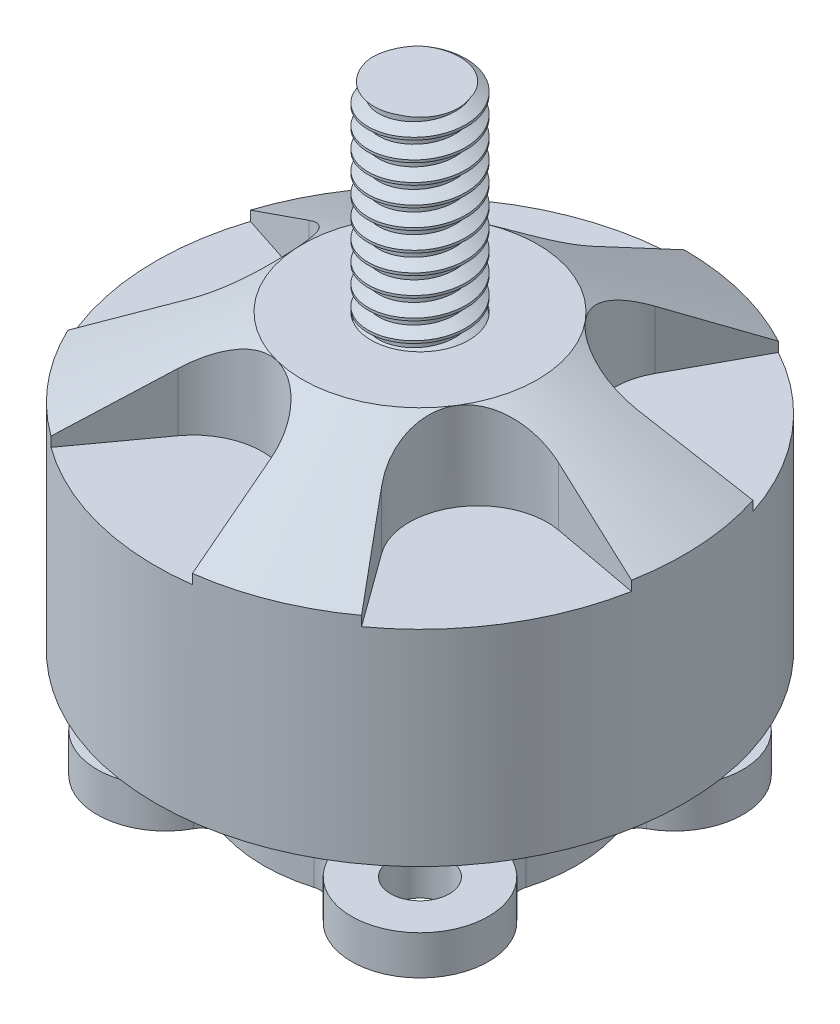
SolidWorks part; units mm, degrees
ref_plane "Front Plane" through (0, 0, 0) normal (0, 0, 1) x (1, 0, 0)
ref_plane "Top Plane" through (0, 0, 0) normal (0, 1, 0) x (1, 0, 0)
ref_plane "Right Plane" through (0, 0, 0) normal (1, 0, 0) x (0, 0, -1)
sketch "Sketch3" plane through (0, 0, 0) normal (0, 1, 0) x (1, 0, 0)
  line L1 (-6.5, 6.5) -> (6.5, -6.5) construction
  line L2 (8, 3.3377) -> (8, -3.3377) construction
  line L3 (-8, 3.3377) -> (-8, -3.3377) construction
  line L4 (-3.3377, -8) -> (3.3377, -8) construction
  line L5 (-3.3377, 8) -> (3.3377, 8) construction
  line L6 (-10, 6.5) -> (-10, -6.5) construction
  line L7 (-6.5, -10) -> (6.5, -10) construction
  line L8 (10, -6.5) -> (10, 6.5) construction
  circle A0 centre (6.5, 6.5) radius 1.5
  circle A1 centre (6.5, -6.5) radius 1.5
  circle A2 centre (-6.5, -6.5) radius 1.5
  circle A3 centre (-6.5, 6.5) radius 1.5
  arc A4 (7.3707, 3.11) -> (3.11, 7.3707) centre (6.5, 6.5) ccw
  arc A5 (3.11, -7.3707) -> (7.3707, -3.11) centre (6.5, -6.5) ccw
  arc A6 (-7.3707, -3.11) -> (-3.11, -7.3707) centre (-6.5, -6.5) ccw
  arc A7 (-3.11, 7.3707) -> (-7.3707, 3.11) centre (-6.5, 6.5) ccw
  arc A8 (-7.3707, 3.11) -> (-7.3707, -3.11) centre (0, 0) ccw
  arc A9 (3.11, 7.3707) -> (-3.11, 7.3707) centre (0, 0) ccw
  arc A10 (7.3707, -3.11) -> (7.3707, 3.11) centre (0, 0) ccw
  arc A12 (-3.11, -7.3707) -> (3.11, -7.3707) centre (0, 0) ccw
  point P15 (0, 0)
  dimension "D3" = 3
  dimension "D4" = 2
  dimension "D5" = 2
  dimension "D1" = 13
  dimension "D2" = 13
  dimension "D6" = 2
  dimension "D7" = 2
  dimension "D8" = 1.5
extrude "Boss-Extrude3" add sketch "Sketch3" along normal blind 2
fillet "Fillet1" radius 1 8 edges at (-7.3707, 1, 3.11) (-7.3707, 1, -3.11) (3.11, 1, -7.3707) (-3.11, 1, -7.3707) (7.3707, 1, 3.11) (7.3707, 1, -3.11) (-3.11, 1, 7.3707) (3.11, 1, 7.3707)
sketch "Sketch4" plane through (0, 2, 0) normal (0, 1, 0) x (1, 0, 0)
  circle A0 centre (0, 0) radius 5
  dimension "D1" = 10
extrude "Boss-Extrude4" add sketch "Sketch4" along normal blind 3.5
sketch "Sketch1" plane through (0, 5.5, 0) normal (0, 1, 0) x (1, 0, 0)
  circle A0 centre (0, 0) radius 13.5
  dimension "D1" = 27
extrude "Boss-Extrude5" add sketch "Sketch1" along normal blind 15
sketch "Sketch5" plane through (0, 20.5, 0) normal (0, 1, 0) x (1, 0, 0)
  circle A0 centre (0, 0) radius 2.5
  dimension "D1" = 5
extrude "Boss-Extrude6" add sketch "Sketch5" along normal blind 10
fillet "Fillet3" radius 1.5 1 edges at (0, 2, 5)
thread "Thread1" pitch 1 method cut profile "Thread Profile1" start angle 0, offset 2, length 15, pitch 1, diameter 5
ref_plane "Plane1" through (-2.5, 32.5, 0) normal (0, 0, 1) x (-1, 0, 0)
sketch "Thread Profile1" plane through (-2.5, 32.5, 0) normal (0, 0, 1) x (-1, 0, 0)
  line L0 (0, 0) -> (0, 1) construction
  line L11 (0, 0) -> (0, 0.875)
  line L12 (0, 0.875) -> (-0.5413, 0.5625)
  line L13 (-0.5413, 0.5625) -> (-0.5413, 0.3125)
  line L15 (-0.5413, 0.3125) -> (0, 0)
  line L17 (-0.5413, 0.4375) -> (0, 0.4375) construction
  point P2 (0, 0)
  dimension "Pitch" = 1
  dimension "Profile_Angle" = 60
  dimension "Profile_Land" = 0.25
  dimension "Profile_Height" = 0.5413
sketch "Sketch6" plane through (0, 0, 0) normal (1, 0, 0) x (0, 0, -1)
  line L0 (-13.5, 16.5) -> (-6, 20.5)
  line L1 (-13.5, 20.5) -> (-13.5, 5.5) construction
  line L2 (13.5, 20.5) -> (-13.5, 20.5) construction
  line L3 (-6, 20.5) -> (-13.5, 20.5)
  line L4 (-13.5, 20.5) -> (-13.5, 16.5)
  line L5 (-13.5, 5.5) -> (13.5, 5.5) construction
  dimension "D1" = 11
  dimension "D2" = 6
ref_axis "Axis1" through (0, 20.5, 0) along (0, -1, 0)
revolve "Cut-Revolve1" cut sketch "Sketch6" angle 360 about axis through (0, 20.5, 0) along (0, -1, 0)
ref_plane "Plane2" through (0, 20.5, 0) normal (0, 1, 0) x (1, 0, 0)
sketch "Sketch7" plane through (0, 20.5, 0) normal (0, 1, 0) x (1, 0, 0)
  line L0 (0, 0) -> (-9.2888, 9.7963)
  line L1 (0, 0) -> (0, 13.5)
  line L2 (0, 0) -> (-5, 12.5399) construction
  circle A0 centre (0, 0) radius 13.5 construction
  circle A1 centre (0, 0) radius 6 construction
  arc A2 (0, 6) -> (-4.1284, 4.3539) centre (0, 0) ccw
  arc A3 (0, 13.5) -> (-9.2888, 9.7963) centre (0, 0) ccw
  arc A4 (-6.0905, 6.4233) -> (0, 8.8517) centre (-3.5294, 8.8517) ccw
  dimension "D1" = 10
extrude "Cut-Extrude2" cut sketch "Sketch7" against normal blind 4.5 contours A4 L2 A3 L0 | L2 A4 L1 A3 region at (-5.5475, 20.5, -8.745) region at (-1.9915, 20.5, -10.1628)
pattern_circular "CirPattern1" count 5 over 360 about axis through (0, 20.5, 0) along (0, -1, 0) of "Cut-Extrude2"
